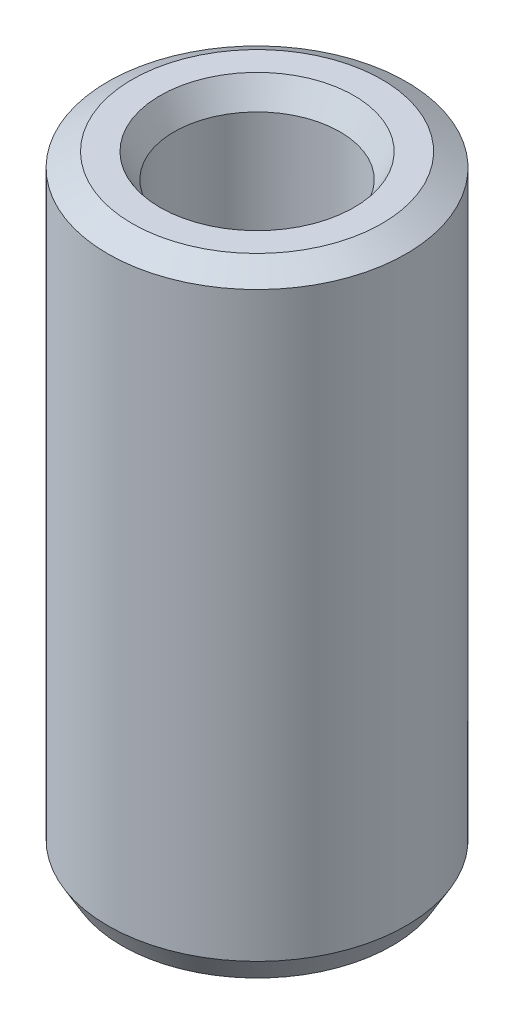
SolidWorks part; units mm, degrees
ref_plane "Front Plane" through (0, 0, 0) normal (0, 0, 1) x (1, 0, 0)
ref_plane "Top Plane" through (0, 0, 0) normal (0, 1, 0) x (1, 0, 0)
ref_plane "Right Plane" through (0, 0, 0) normal (1, 0, 0) x (0, 0, -1)
sketch "Sketch1" plane through (0, 0, 0) normal (0, 1, 0) x (1, 0, 0)
  circle A0 centre (0, 0) radius 5
  dimension "SLEEVE_OD" = 10
extrude "Boss-Extrude1" add sketch "Sketch1" along normal blind 20.7877
sketch "Sketch2" plane through (0, 0, 0) normal (0, 1, 0) x (1, 0, 0)
  circle A0 centre (0, 0) radius 2.7788
  dimension "BORE_D" = 5.5576
extrude "Cut-Extrude1" cut sketch "Sketch2" along normal through all
chamfer "Chamfer1" distance 0.4709 angle 60 4 edges at (0, 20.7877, 2.7788) (0, 0, 2.7788) (0, 0, 5) (0, 20.7877, 5) first distance on face at (0, 20.7877, 2.7788) first distance on face at (0, 0, 2.7788) first distance on face at (0, 20.7877, 5)
